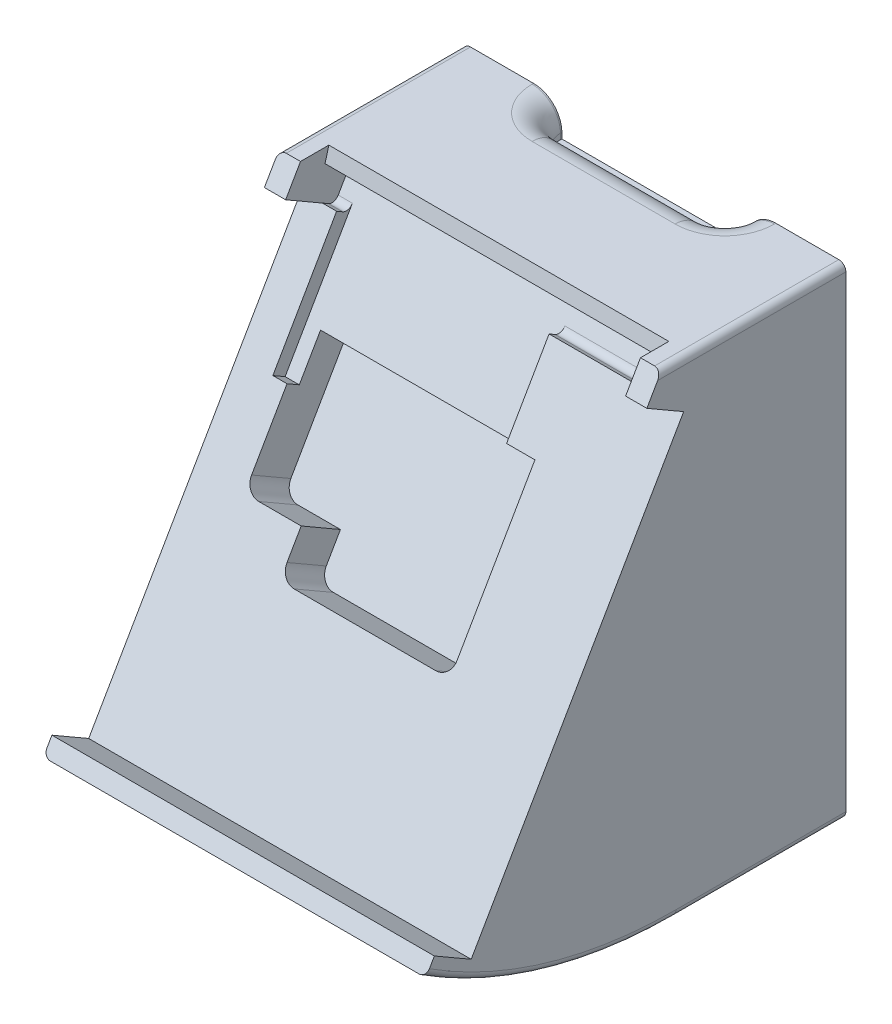
SolidWorks part; units mm, degrees
ref_plane "前视基准面" through (0, 0, 0) normal (0, 0, 1) x (1, 0, 0)
ref_plane "上视基准面" through (0, 0, 0) normal (0, 1, 0) x (1, 0, 0)
ref_plane "右视基准面" through (0, 0, 0) normal (1, 0, 0) x (0, 0, -1)
sketch "草图2" plane through (0, 0, 0) normal (1, 0, 0) x (0, 0, -1)
  line L0 (0, 0) -> (0, 34)
  line L1 (0, 0) -> (-12, 0)
  line L2 (0, 34) -> (-13, 34)
  line L3 (-13, 34) -> (-14.05, 32.1813)
  line L4 (-14.05, 32.1813) -> (-11.4519, 30.6813)
  line L5 (-11.4519, 30.6813) -> (-26.4519, 4.7006)
  line L6 (-26.4519, 4.7006) -> (-29.05, 6.2006)
  line L7 (-29.05, 6.2006) -> (-29.65, 5.1614)
  arc A0 (-12, 0) -> (-29.65, 5.1614) centre (-12, 32.759) cw
  dimension "D1" = 34
  dimension "D2" = 13
  dimension "D3" = 12
  dimension "D4" = 120
  dimension "D5" = 2.1
  dimension "D6" = 3
  dimension "D7" = 30
  dimension "D8" = 3
  dimension "D9" = 1.2
extrude "凸台-拉伸1" add sketch "草图2" along normal blind 27
ref_plane "基准面1" through (13.5, 0, 0) normal (1, 0, 0) x (0, 0, -1)
sketch "草图3" plane through (13.5, 0, 0) normal (1, 0, 0) x (0, 0, -1)
  line L0 (-13, 34) -> (-11, 34)
  line L1 (0, 34) -> (-13, 34) construction
  line L2 (-11, 34) -> (-11.2679, 33)
  line L3 (-11.2679, 33) -> (-9.5359, 32)
  line L4 (-9.5359, 32) -> (-10.5859, 30.1813)
  line L6 (-14.05, 32.1813) -> (-11.4519, 30.6813) construction
  line L7 (-14.05, 32.1813) -> (-11.4519, 30.6813) construction
  line L8 (-11.4519, 30.6813) -> (-8.6837, 29.0831) construction
  line L9 (-10.5859, 30.1813) -> (-14.05, 32.1813)
  line L10 (-14.05, 32.1813) -> (-13, 34)
  dimension "D1" = 2
  dimension "D2" = 105
  dimension "D4" = 2
  dimension "D5" = 2.1
extrude "切除-拉伸1" cut sketch "草图3" against normal mid plane 24
sketch "草图4" plane through (0, 12.6292, 21.8744) normal (0, 0.5, 0.866) x (1, 0, 0)
  line L0 (2.5, 20.8449) -> (2.5, 11.8449)
  line L1 (1.5, 20.8449) -> (25.5, 20.8449) construction
  line L2 (0, 20.8449) -> (0, -9.1551) construction
  line L3 (17.5, 20.8449) -> (17.5, 11.8449)
  line L4 (25.5, 20.8449) -> (1.5, 20.8449) construction
  line L5 (2.5, 11.8449) -> (17.5, 11.8449)
  line L6 (2.5, 20.8449) -> (17.5, 20.8449)
  dimension "D1" = 2.5
  dimension "D2" = 9
  dimension "D3" = 15
extrude "切除-拉伸2" cut sketch "草图4" against normal blind 1
sketch "草图5" plane through (0, 12.6292, 21.8744) normal (0, 0.5, 0.866) x (1, 0, 0)
  line L0 (3.5, 14.8449) -> (3.5, 5.8449)
  line L1 (19.5, 14.8449) -> (19.5, 2.8449)
  line L2 (0, 20.8449) -> (0, -9.1551) construction
  line L3 (3.5, 14.8449) -> (19.5, 14.8449)
  line L4 (1.5, 20.8449) -> (2.5, 20.8449) construction
  line L5 (3.5, 5.8449) -> (7.5, 5.8449)
  line L6 (7.5, 5.8449) -> (7.5, 2.8449)
  line L7 (7.5, 2.8449) -> (19.5, 2.8449)
  dimension "D1" = 3.5
  dimension "D2" = 6
  dimension "D3" = 9
  dimension "D4" = 4
  dimension "D5" = 3
  dimension "D6" = 12
extrude "切除-拉伸3" cut sketch "草图5" against normal blind 3.2
sketch "草图7" plane through (13.5, 0, 0) normal (1, 0, 0) x (0, 0, -1)
  line L0 (0, 34) -> (-13, 34) construction
  line L1 (0, 0) -> (0, 34) construction
  line L2 (0, 28.5) -> (0, 22.5)
  line L3 (-11.6806, 23.8852) -> (-12.9797, 24.6352)
  line L4 (-11.6806, 23.8852) -> (-13.5859, 24.9852) construction
  line L5 (-11.6806, 23.8852) -> (-13.5859, 24.9852) construction
  line L6 (0, 22.5) -> (0, 20.3983) construction
  spline S0 degree 3 poles (0, 22.5) (0, 24.1071) (-4.658, 26.4783) (-9.8564, 27.0449) (-11.6806, 23.8852) knots 0 0 0 0 0.336909 1 1 1 1
  spline S1 degree 3 poles (0, 28.5) (-2.5754, 28.5) (-7.0348, 28.8913) (-11.4375, 27.3062) (-12.9797, 24.6352) knots 0 0 0 0 0.497674 1 1 1 1
  point P10 (0, 20.3983)
  dimension "D1" = 6
  dimension "D2" = 5.5
  dimension "D3" = 5.6
  dimension "D4" = 7
  dimension "D5" = 3.2
  dimension "D6" = 3
  dimension "D7" = 1.5
extrude "切除-拉伸4" cut sketch "草图7" against normal mid plane 10
fillet "圆角1" radius 1 3 edges at (19.5, 14.2929, 19.0663) (7.5, 14.2929, 19.0663) (3.5, 16.891, 17.5663)
fillet "圆角2" radius 0.5 3 edges at (21.5, 30.1813, 10.5859) (2, 30.1813, 10.5859) (13.5, 32, 9.5359)
fillet "圆角3" radius 0.2 3 edges at (18.5, 24.2602, 12.3302) (8.5, 24.2602, 12.3302) (13.5, 24.6352, 12.9797)
sketch "草图8" plane through (0, 34, 0) normal (0, 1, 0) x (1, 0, 0)
  line L0 (27, 0) -> (0, 0) construction
  line L1 (27, 0) -> (0, 0) construction
  line L2 (13.5, 0) -> (13.5, -11) construction
  line L3 (1.5, -11) -> (25.5, -11) construction
  line L5 (6.95, -1.6) -> (20.05, -1.6)
  line L6 (6.95, -1.6) -> (6.95, 0)
  line L7 (6.95, 0) -> (20.05, 0)
  line L8 (20.05, -1.6) -> (20.05, 0)
  line L9 (6.95, -1.6) -> (20.05, 0) construction
  line L10 (6.95, 0) -> (20.05, -1.6) construction
  point P6 (13.5, -0.8)
  dimension "D1" = 13.1
  dimension "D2" = 1.6
extrude "切除-拉伸5" cut sketch "草图8" against normal blind 2.4
fillet "圆角4" radius 1.5 2 edges at (6.95, 32.8, 1.6) (20.05, 32.8, 1.6)
fillet "圆角5" radius 2 5 edges at (20.05, 34, 0.05) (6.95, 34, 0.05) (7.3893, 34, 1.1607) (13.5, 34, 1.6) (19.6107, 34, 1.1607)
fillet "圆角6" radius 0.5 6 edges at (0, 1.3168, 21.1946) (27, 1.3168, 21.1946) (0, 0, 6) (27, 0, 6) (27, 34, 6.5) (0, 34, 6.5)
sketch "草图9" plane through (0, 0, 0) normal (0, 0, -1) x (-1, 0, 0)
  line L0 (0, 17) -> (-27, 17) construction
  line L1 (0, 0.5) -> (0, 33.5) construction
  line L2 (-27, 0.5) -> (-27, 33.5) construction
  line L3 (-13.5, 17) -> (-13.5, 0) construction
  line L4 (-26.5, 0) -> (-0.5, 0) construction
  circle A0 centre (-23.5, 30.5) radius 1.575
  circle A1 centre (-3.5, 30.5) radius 1.575
  circle A2 centre (-3.5, 3.5) radius 1.575
  circle A3 centre (-23.5, 3.5) radius 1.575
  dimension "D3" = 3.15
  dimension "D1" = 10
  dimension "D2" = 13.5
extrude "切除-拉伸6" cut sketch "草图9" against normal blind 3.1
